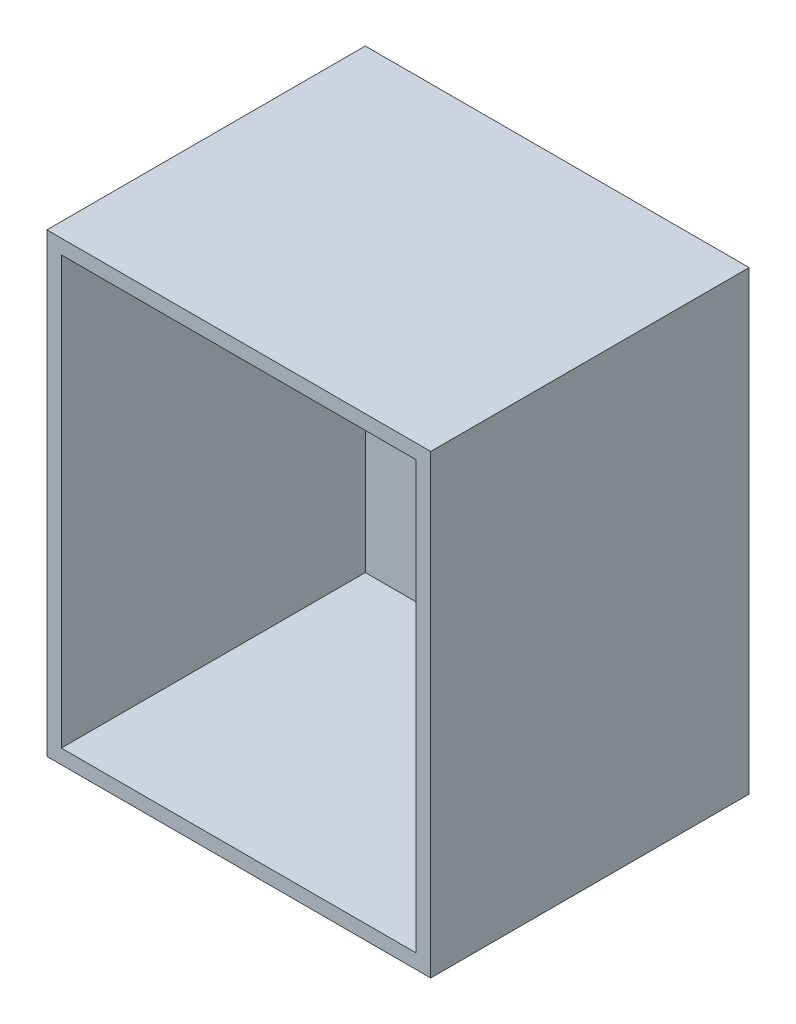
SolidWorks part; units mm, degrees
ref_plane "Piano frontale" through (0, 0, 0) normal (0, 0, 1) x (1, 0, 0)
ref_plane "Piano superiore" through (0, 0, 0) normal (0, 1, 0) x (1, 0, 0)
ref_plane "Piano destro" through (0, 0, 0) normal (1, 0, 0) x (0, 0, -1)
sketch "Schizzo1" plane through (0, 0, 0) normal (0, 0, 1) x (1, 0, 0)
  line L1 (0, 0) -> (50.5, 0)
  line L2 (0, 0) -> (0, 60)
  line L3 (0, 60) -> (50.5, 60)
  line L4 (50.5, 0) -> (50.5, 60)
  dimension "D1" = 50.5
  dimension "D2" = 60
extrude "Estrusione-Estrusione1" add sketch "Schizzo1" along normal blind 1.9
sketch "Schizzo2" plane through (0, 0, 1.9) normal (0, 0, 1) x (1, 0, 0)
  line L0 (0, 0) -> (50.5, 0) construction
  line L1 (0, 60) -> (1.9, 60)
  line L2 (0, 60) -> (0, 0)
  line L3 (0, 0) -> (1.9, 0)
  line L4 (1.9, 60) -> (1.9, 0)
  dimension "D1" = 1.9
extrude "Estrusione-Estrusione2" add sketch "Schizzo2" along normal blind 40
sketch "Schizzo3" plane through (0, 0, 1.9) normal (0, 0, 1) x (1, 0, 0)
  line L0 (50.5, 0) -> (50.5, 60) construction
  line L1 (1.9, 0) -> (50.5, 0)
  line L2 (1.9, 0) -> (1.9, 1.9)
  line L3 (1.9, 1.9) -> (50.5, 1.9)
  line L4 (50.5, 0) -> (50.5, 1.9)
  dimension "D1" = 1.9
extrude "Estrusione-Estrusione3" add sketch "Schizzo3" along normal blind 40
sketch "Schizzo4" plane through (0, 0, 1.9) normal (0, 0, 1) x (1, 0, 0)
  line L0 (50.5, 60) -> (1.9, 60) construction
  line L1 (50.5, 1.9) -> (48.6, 1.9)
  line L2 (50.5, 1.9) -> (50.5, 60)
  line L3 (50.5, 60) -> (48.6, 60)
  line L4 (48.6, 1.9) -> (48.6, 60)
  dimension "D1" = 1.9
extrude "Estrusione-Estrusione4" add sketch "Schizzo4" along normal blind 40
sketch "Schizzo5" plane through (0, 0, 1.9) normal (0, 0, 1) x (1, 0, 0)
  line L0 (48.6, 60) -> (48.6, 1.9) construction
  line L1 (1.9, 60) -> (48.6, 60)
  line L2 (1.9, 60) -> (1.9, 58.1)
  line L3 (1.9, 58.1) -> (48.6, 58.1)
  line L4 (48.6, 60) -> (48.6, 58.1)
  dimension "D1" = 1.9
extrude "Estrusione-Estrusione5" add sketch "Schizzo5" along normal blind 40
